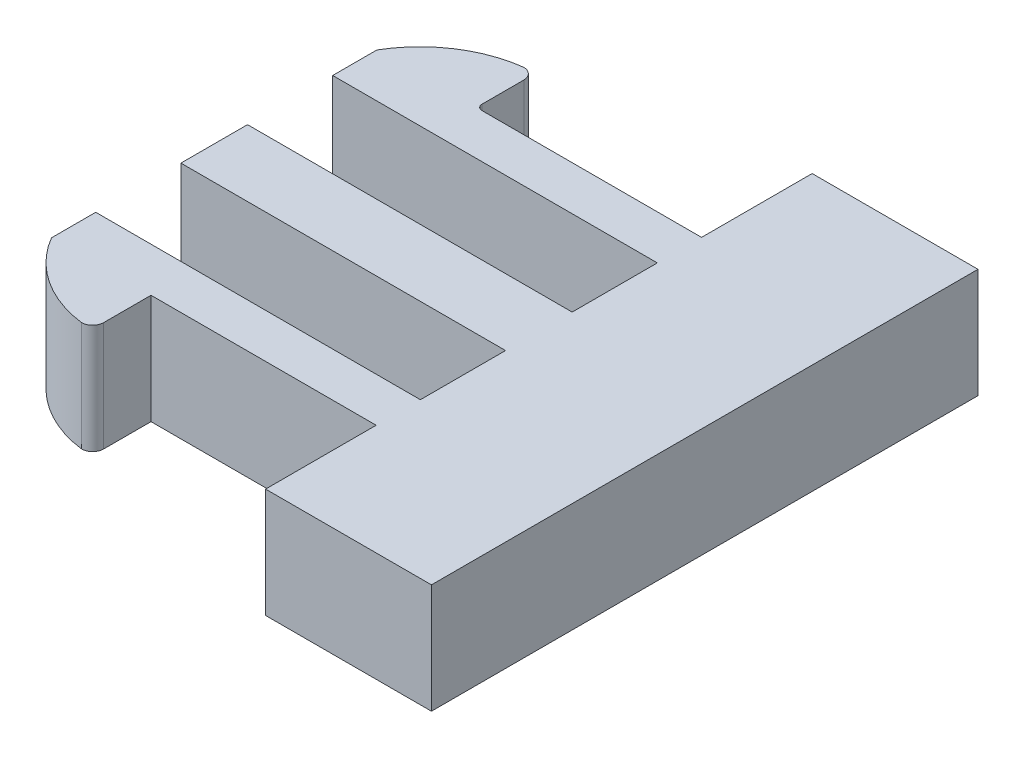
SolidWorks part; units mm, degrees
ref_plane "Alzado" through (0, 0, 0) normal (0, 0, 1) x (1, 0, 0)
ref_plane "Planta" through (0, 0, 0) normal (0, 1, 0) x (1, 0, 0)
ref_plane "Vista lateral" through (0, 0, 0) normal (1, 0, 0) x (0, 0, -1)
sketch "Croquis1" plane through (0, 0, 0) normal (0, 1, 0) x (1, 0, 0)
  line L0 (13.2702, -24.7145) -> (13.2702, -14.7145)
  line L1 (13.2702, 24.7145) -> (13.2702, 14.7145)
  line L2 (13.2702, 24.7145) -> (28.2702, 24.7145)
  line L3 (28.2702, 24.7145) -> (28.2702, -24.7145)
  line L5 (13.2702, -24.7145) -> (28.2702, -24.7145)
  line L6 (13.2702, -14.7145) -> (28.2702, -14.7145) construction
  line L7 (-6.9906, 14.7145) -> (28.2702, 14.7145) construction
  line L8 (-7.0906, 15.2145) -> (-7.0906, 18.9955)
  line L11 (28.2702, 0) -> (-28.1565, 0) construction
  line L12 (-6.5906, 14.7145) -> (13.2702, 14.7145)
  line L13 (-16.0906, 14.7145) -> (-16.0906, 10.7145)
  line L14 (-16.0906, 10.7145) -> (13.2702, 10.7145)
  line L15 (13.2702, 10.7145) -> (13.2702, 8.2145)
  line L17 (-16.0906, 3.0122) -> (-16.0906, -3.0122)
  line L20 (-16.0906, -10.7145) -> (13.2702, -10.7145)
  line L21 (-16.0906, -14.7145) -> (-16.0906, -10.7145)
  line L23 (-7.0906, -18.9955) -> (-7.0906, -14.7145)
  line L24 (13.2702, -14.7145) -> (-7.0906, -14.7145)
  line L25 (13.2702, 8.2145) -> (13.2702, 5.2122)
  line L29 (13.2702, 5.2122) -> (13.2702, 5.0122)
  line L35 (-16.0906, 10.7145) -> (-16.0906, 5.2145) construction
  line L36 (-16.0906, 3.0122) -> (13.2702, 3.0122)
  line L37 (13.2702, 3.0122) -> (13.2702, 5.0122)
  line L38 (13.2702, -10.7145) -> (13.2702, -8.2145)
  line L39 (13.2702, -3.0122) -> (13.2702, -5.0122)
  line L40 (-16.0906, -3.0122) -> (13.2702, -3.0122)
  line L41 (13.2702, -5.2122) -> (13.2702, -5.0122)
  line L42 (13.2702, -8.2145) -> (13.2702, -5.2122)
  arc A0 (-7.0906, 18.9955) -> (-8.0906, 19.9955) centre (-8.0906, 18.9955) ccw
  arc A2 (-6.5906, 14.7145) -> (-7.0906, 15.2145) centre (-6.5906, 15.2145) cw
  arc A4 (-7.0906, -18.9955) -> (-8.0906, -19.9955) centre (-8.0906, -18.9955) cw
  arc A5 (-16.0906, -14.7145) -> (-8.0906, -19.9955) centre (-6.7369, -9.2447) ccw
  arc A6 (-16.0906, 14.7145) -> (-8.0906, 19.9955) centre (-6.7369, 9.2447) cw
  point P30 (-16.0906, 0)
  point P39 (-16.0906, 0)
  point P48 (-16.0906, 0)
  dimension "D2" = 1
  dimension "D3" = 10.8356
  dimension "D4" = 0.5
  dimension "D1" = 10
  dimension "D5" = 4
  dimension "D6" = 2.5
  dimension "D7" = 15
  dimension "D8" = 49.429
  dimension "D9" = 5.5
  dimension "0.2" = 0.2
  dimension "D10" = 29.3608
extrude "Saliente-Extruir1" add sketch "Croquis1" along normal blind 9.9 contours A4 L23 L24 L0 L5 L3 L2 L1 L12 A2 L8 A0 L13 L14 L15 L17 L20 L21 region at (11.564, 0, -0.0007)
